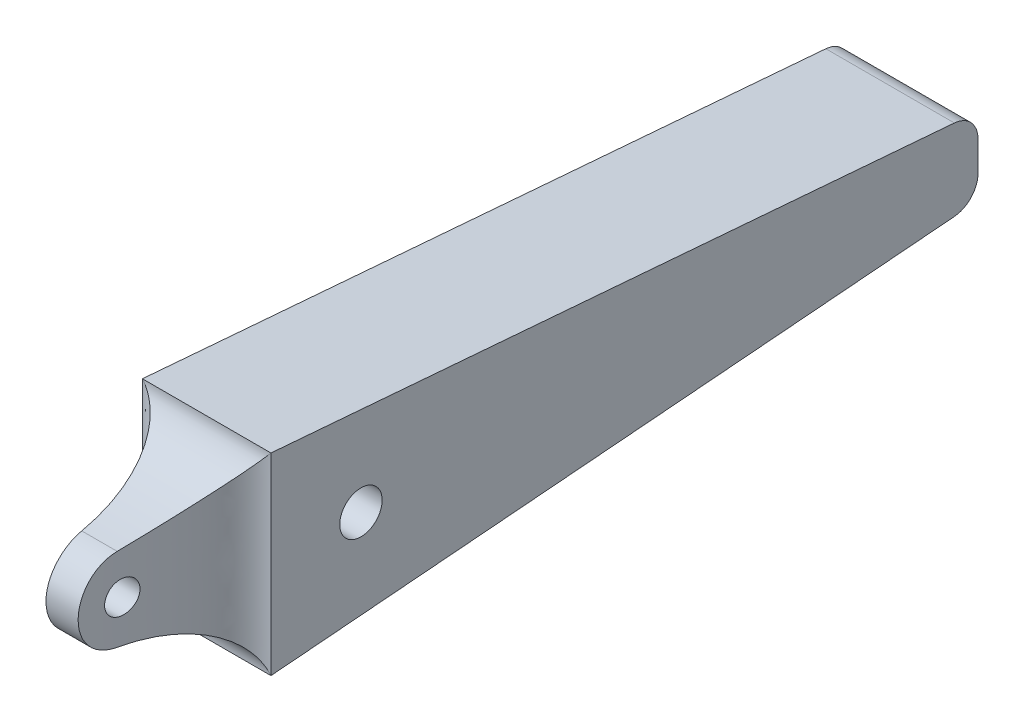
SolidWorks part; units mm, degrees
ref_plane "Front Plane" through (0, 0, 0) normal (1, 0, 0) x (0, 1, 0)
ref_plane "Top Plane" through (0, 0, 0) normal (0, 0, 1) x (0, 1, 0)
ref_plane "Right Plane" through (0, 0, 0) normal (0, 1, 0) x (-1, 0, 0)
sketch "Sketch1" plane through (0, 0, 0) normal (1, 0, 0) x (0, 1, 0)
  line L0 (0, -28.3905) -> (0, 48) construction
  line L1 (3, 0) -> (-3, 0)
  line L2 (-3, 0) -> (-7.5, 55)
  line L3 (3, 0) -> (7.5, 55)
  line L4 (0, 66.25) -> (0, 51.4514) construction
  circle A1 centre (0, 63) radius 1.25
  circle A2 centre (0, 48) radius 1.65
  arc A3 (3.2322, 63.3399) -> (-3.2322, 63.3399) centre (0, 63) ccw
  ellipse E0 centre (-7.5, 66.25) end of major axis (-7.5, 77.5) minor radius 4.4182 (-7.5, 55) -> (-3.2322, 63.3399) ccw
  ellipse E1 centre (7.5, 66.25) end of major axis (7.5, 77.5) minor radius 4.4182 (7.5, 55) -> (3.2322, 63.3399) cw
  point P9 (0, 0)
  dimension "D4" = 2.5
  dimension "D5" = 3.3
  dimension "D7" = 7
  dimension "D8" = 2
  dimension "D1" = 15
  dimension "D2" = 6
  dimension "D3" = 55
  dimension "D6" = 15
extrude "Boss-Extrude1" add sketch "Sketch1" along normal blind 10
fillet "Fillet3" radius 2 2 edges at (5, 3, 0) (5, -3, 0)
sketch "Sketch4" plane through (0, 0, 0) normal (0, 1, 0) x (-1, 0, 0)
  line L0 (-5, 55) -> (-5, 70.3533) construction
  line L1 (-10, 55) -> (0, 55) construction
  ellipse E0 centre (-10, 66.25) end of major axis (-10, 77.5) minor radius 3.75
  ellipse E1 centre (0, 66.25) end of major axis (0, 77.5) minor radius 3.75
  dimension "D1" = 1.25
extrude "Cut-Extrude3" cut sketch "Sketch4" against normal blind 19.5 and the other way blind 19.5
